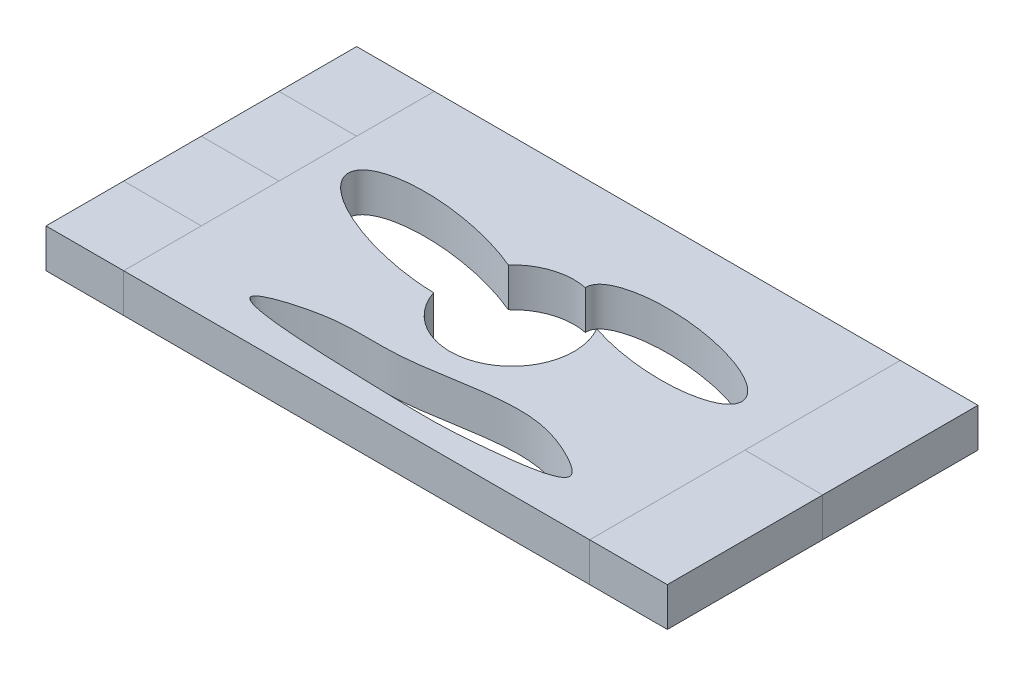
SolidWorks part; units mm, degrees
material "6061 Alloy"
ref_plane "Front Plane" through (0, 0, 0) normal (0, 0, 1) x (1, 0, 0)
ref_plane "Top Plane" through (0, 0, 0) normal (0, 1, 0) x (1, 0, 0)
ref_plane "Right Plane" through (0, 0, 0) normal (1, 0, 0) x (0, 0, -1)
sketch "Sketch1" plane through (0, 0, 0) normal (0, 1, 0) x (1, 0, 0)
  line L1 (-19.05, -12.7) -> (19.05, -12.7)
  line L2 (-19.05, -12.7) -> (-19.05, 12.7)
  line L3 (-19.05, 12.7) -> (19.05, 12.7)
  line L4 (19.05, -12.7) -> (19.05, 12.7)
  line L5 (-19.05, -12.7) -> (19.05, 12.7) construction
  line L6 (-19.05, 12.7) -> (19.05, -12.7) construction
  circle A0 centre (0, 0) radius 5.08
  point P0 (0, 0)
  dimension "D3" = 10.16
  dimension "D1" = 38.1
  dimension "D2" = 25.4
extrude "Boss-Extrude1" add sketch "Sketch1" along normal blind 3.175
sketch "Sketch2" plane through (-19.05, 0, 0) normal (-1, 0, 0) x (0, 0, 1)
  line L0 (-12.7, 0) -> (12.7, 0) construction
  line L3 (-12.7, 3.175) -> (-6.35, 3.175)
  line L4 (-12.7, 3.175) -> (-12.7, 0)
  line L5 (-12.7, 0) -> (-6.35, 0)
  line L6 (-6.35, 3.175) -> (-6.35, 0)
  line L7 (-12.7, 3.175) -> (12.7, 3.175) construction
  line L8 (-6.35, 0) -> (0, 0)
  line L9 (-6.35, 0) -> (-6.35, 3.175)
  line L10 (-6.35, 3.175) -> (0, 3.175)
  line L11 (0, 0) -> (0, 3.175)
  line L13 (0, 3.175) -> (6.35, 3.175)
  line L14 (0, 3.175) -> (0, 0)
  line L15 (0, 0) -> (6.35, 0)
  line L16 (6.35, 3.175) -> (6.35, 0)
  line L17 (6.35, 3.175) -> (12.7, 3.175)
  line L18 (6.35, 3.175) -> (6.35, 0)
  line L19 (6.35, 0) -> (12.7, 0)
  line L20 (12.7, 3.175) -> (12.7, 0)
  line M11 (-12.7, 0) -> (12.7, 0)
  line M12 (12.7, 0) -> (12.7, 3.175)
  line M13 (12.7, 3.175) -> (-12.7, 3.175)
  line M14 (-12.7, 3.175) -> (-12.7, 0)
  dimension "D1" = 6.35
  dimension "D2" = 6.35
extrude "Boss-Extrude3" add sketch "Sketch2" along normal blind 6.35 separate body contours L6 M13 M14 M11 region at (-19.05, 1.5875, -9.525)
extrude "Boss-Extrude4" add sketch "Sketch2<4>" along normal blind 6.35 separate body contours L11 L6 M11 M13 region at (-19.05, 1.5875, -3.175)
sketch "Sketch2<4>" plane through (-19.05, 0, 0) normal (-1, 0, 0) x (0, 0, 1) same geometry as "Sketch2"
extrude "Boss-Extrude6" add sketch "Sketch2<6>" along normal blind 6.35 separate body contours L16 L11 M13 M11 region at (-19.05, 1.5875, 3.175)
sketch "Sketch2<6>" plane through (-19.05, 0, 0) normal (-1, 0, 0) x (0, 0, 1) same geometry as "Sketch2"
extrude "Boss-Extrude7" add sketch "Sketch2<7>" along normal blind 6.35 separate body contours L16 M13 M11 M12 region at (-19.05, 1.5875, 9.525)
sketch "Sketch2<7>" plane through (-19.05, 0, 0) normal (-1, 0, 0) x (0, 0, 1) same geometry as "Sketch2"
sketch "Sketch4" plane through (19.05, 0, 0) normal (1, 0, 0) x (0, 0, -1)
  line L0 (-12.7, 0) -> (12.7, 0) construction
  line L1 (-12.7, 0) -> (0, 0)
  line L2 (-12.7, 0) -> (-12.7, 3.175)
  line L3 (-12.7, 3.175) -> (0, 3.175)
  line L4 (0, 0) -> (0, 3.175)
  line L5 (-12.7, 3.175) -> (-12.7, 0) construction
  line L6 (-12.7, 3.175) -> (12.7, 3.175) construction
  line L8 (0, 3.175) -> (12.7, 3.175)
  line L9 (0, 3.175) -> (0, 0)
  line L10 (0, 0) -> (12.7, 0)
  line L11 (12.7, 3.175) -> (12.7, 0)
  line M1 (-12.7, 0) -> (12.7, 0)
  line M2 (12.7, 0) -> (12.7, 3.175)
  line M3 (12.7, 3.175) -> (-12.7, 3.175)
  line M4 (-12.7, 3.175) -> (-12.7, 0)
extrude "Boss-Extrude8" add sketch "Sketch4" along normal blind 6.35 separate body contours L4 M1 M3 M4 region at (19.05, 1.5875, 6.35)
extrude "Boss-Extrude9" add sketch "Sketch4<3>" along normal blind 6.35 separate body contours L4 M1 M2 M3 region at (19.05, 1.5875, -6.35)
sketch "Sketch4<3>" plane through (19.05, 0, 0) normal (1, 0, 0) x (0, 0, -1) same geometry as "Sketch4"
sketch "Sketch6" plane through (0, 3.175, 0) normal (0, 1, 0) x (1, 0, 0)
  ellipse E0 centre (-8.3808, 1.8124) end of major axis (0, 0) minor radius 2.944
  ellipse E1 centre (8.253, 4.1976) end of major axis (1.0332, 5.2064) minor radius 2.5068
  point P7 (-14.4356, 0.6711)
  point P14 (19.8617, -1.1006)
  point P15 (13.0022, 2.4827)
  point P16 (-16.6879, 3.6089)
extrude "Cut-Extrude1" cut sketch "Sketch6" against normal through all
sketch "Sketch7" plane through (0, 3.175, 0) normal (0, 1, 0) x (1, 0, 0)
  spline S0 degree 3 poles (-16.5044, -10.237) (-6.8822, -7.1939) (-1.1591, -7.8663) (5.8375, -5.8612) (10.7304, -6.7928) (15.4518, -9.5711) (5.8902, -10.8352) (1.731, -10.6282) (-16.5044, -10.237) (-6.8822, -7.1939) (-1.1591, -7.8663) knots -0.483952 -0.310575 -0.082365 0 0.107817 0.283314 0.376887 0.42253 0.516048 0.689425 0.917635 1 1.107817 1.283314 1.376887 only from (-7.7297, -7.7041) to (-7.7297, -7.7041)
  point P2 (11.7737, -7.4993)
  point P4 (-11.8249, -9.035)
  point P6 (-7.7297, -7.7041)
extrude "Cut-Extrude2" cut sketch "Sketch7" against normal through all
